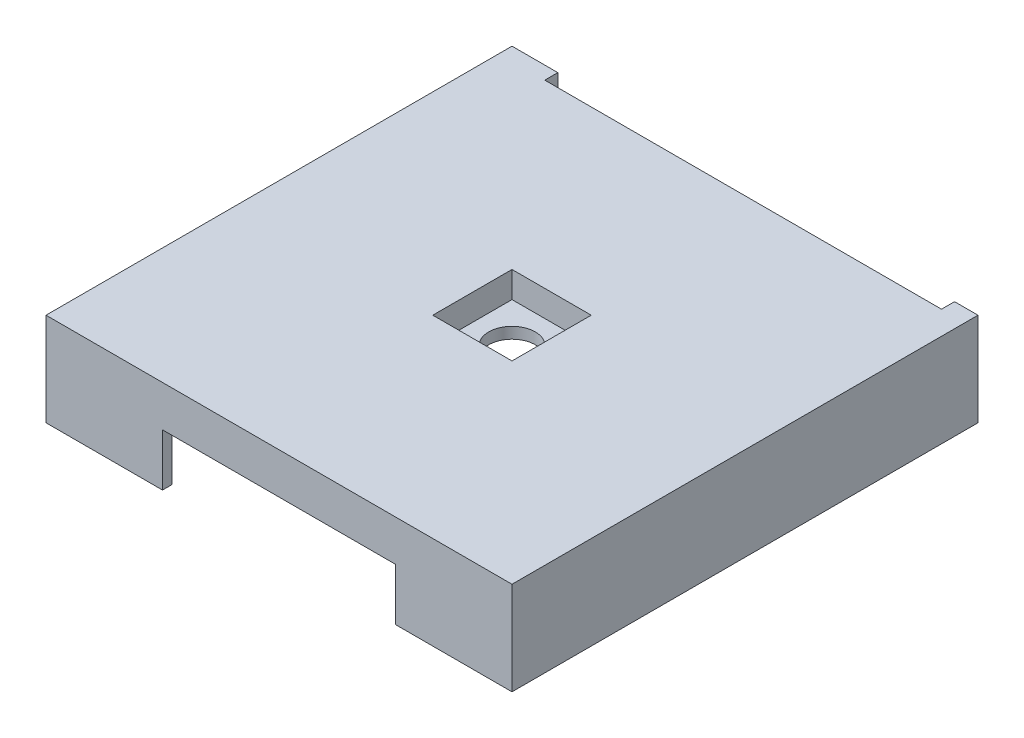
SolidWorks part; units mm, degrees
ref_plane "Ebene vorne" through (0, 0, 0) normal (0, 0, 1) x (1, 0, 0)
ref_plane "Ebene oben" through (0, 0, 0) normal (0, 1, 0) x (1, 0, 0)
ref_plane "Ebene rechts" through (0, 0, 0) normal (1, 0, 0) x (0, 0, -1)
sketch "Skizze1" plane through (0, 0, 0) normal (0, 1, 0) x (1, 0, 0)
  line L1 (-125, -125) -> (125, -125)
  line L2 (-125, -125) -> (-125, 125)
  line L3 (-125, 125) -> (125, 125)
  line L4 (125, -125) -> (125, 125)
  line L5 (-125, -125) -> (125, 125) construction
  line L6 (-125, 125) -> (125, -125) construction
  point P0 (0, 0)
  dimension "D1" = 250
  dimension "D2" = 250
extrude "Aufsatz-Linear austragen1" add sketch "Skizze1" along normal blind 50
sketch "Skizze2" plane through (0, 0, 125) normal (0, 0, 1) x (1, 0, 0)
  line L0 (-62.5, 28) -> (62.5, 28)
  line L2 (-62.5, 28) -> (-62.5, 0)
  line L3 (-62.5, 0) -> (62.5, 0)
  line L4 (-125, 0) -> (125, 0) construction
  line L5 (62.5, 0) -> (62.5, 28)
  point P3 (0, 28)
  dimension "D1" = 125
  dimension "D2" = 28
extrude "Schnitt-Linear austragen1" cut sketch "Skizze2" against normal blind 30
sketch "Skizze3" plane through (0, 0, 0) normal (0, -1, 0) x (1, 0, 0)
  line L0 (62.5, 125) -> (125, 125) construction
  line L1 (-120, -120) -> (120, -120)
  line L2 (-120, -120) -> (-120, 120)
  line L3 (-120, 120) -> (120, 120)
  line L4 (120, -120) -> (120, 120)
  line L5 (-120, -120) -> (120, 120) construction
  line L6 (-120, 120) -> (120, -120) construction
  line L7 (125, 125) -> (125, -125) construction
  point P0 (0, 0)
  dimension "D1" = 5
  dimension "D2" = 5
extrude "Schnitt-Linear austragen2" cut sketch "Skizze3" against normal blind 30
sketch "Skizze4" plane through (0, 50, 0) normal (0, 1, 0) x (1, 0, 0)
  circle A0 centre (0, 0) radius 12.5
extrude "Schnitt-Linear austragen3" cut sketch "Skizze4" against normal blind 30
sketch "Skizze5" plane through (0, 50, 0) normal (0, 1, 0) x (1, 0, 0)
  line L1 (21.25, 21.25) -> (-21.25, 21.25)
  line L2 (21.25, 21.25) -> (21.25, -21.25)
  line L3 (21.25, -21.25) -> (-21.25, -21.25)
  line L4 (-21.25, 21.25) -> (-21.25, -21.25)
  line L5 (21.25, 21.25) -> (-21.25, -21.25) construction
  line L6 (21.25, -21.25) -> (-21.25, 21.25) construction
  point P0 (0, 0)
  dimension "D1" = 42.5
  dimension "D2" = 42.5
extrude "Schnitt-Linear austragen4" cut sketch "Skizze5" against normal offset from surface (14 mm away) 6 up to face at (0, 30, 12.5)
sketch "Skizze6" plane through (0, 0, -125) normal (0, 0, -1) x (-1, 0, 0)
  line L0 (-125, 50) -> (125, 50) construction
  line L1 (-112.4245, 50) -> (100.418, 50)
  line L2 (-112.4245, 50) -> (-112.4245, 0)
  line L3 (-112.4245, 0) -> (100.418, 0)
  line L4 (100.418, 50) -> (100.418, 0)
  line L5 (-125, 0) -> (125, 0) construction
extrude "Schnitt-Linear austragen5" cut sketch "Skizze6" against normal blind 7 contours L2 L1 L4 L3
